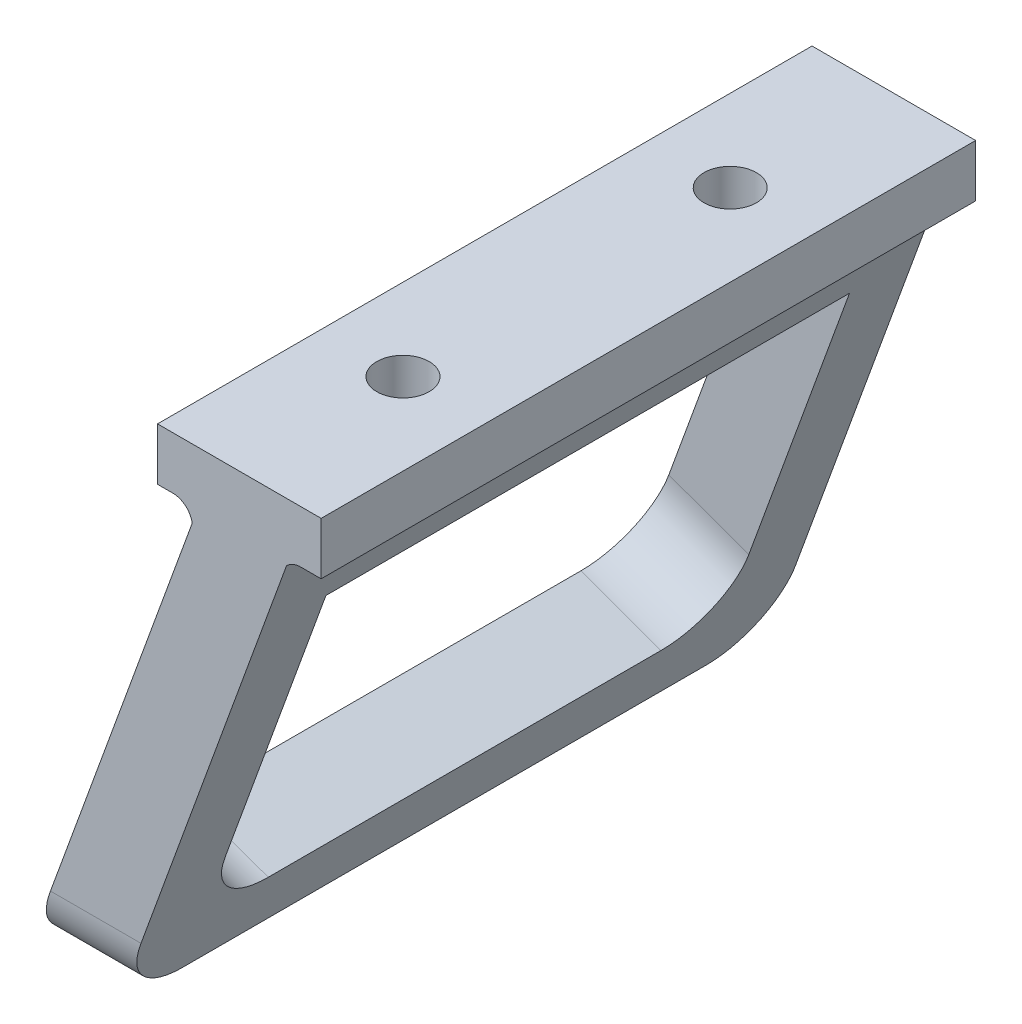
SolidWorks part; units mm, degrees
ref_plane "Front Plane" through (0, 0, 0) normal (0, 0, 1) x (1, 0, 0)
ref_plane "Top Plane" through (0, 0, 0) normal (0, 1, 0) x (1, 0, 0)
ref_plane "Right Plane" through (0, 0, 0) normal (1, 0, 0) x (0, 0, -1)
sketch "Sketch1" plane through (0, 0, 0) normal (0, 0, 1) x (1, 0, 0)
  line L0 (-12.5, 8) -> (12.5, 8)
  line L1 (12.5, 8) -> (12.5, 0)
  line L2 (12.5, 0) -> (9.3758, 0)
  line L3 (7.2, -0.9346) -> (-18.6657, -72)
  line L4 (-18.6657, -72) -> (-32.5, -72)
  line L5 (-32.5, -72) -> (-7.2, -2.4888)
  line L6 (-10.1561, 0) -> (-12.5, 0)
  line L7 (-12.5, 0) -> (-12.5, 8)
  arc A0 (-7.2, -2.4888) -> (-10.1561, 0) centre (-10.1561, -3) ccw
  arc A1 (9.3758, 0) -> (7.2, -0.9346) centre (9.3758, -3) ccw
  point P12 (0, 0)
  point P13 (0, 0)
  point P14 (12.5, 4)
  point P16 (-7.2, -2.9968)
  point P17 (-7.2, -2.9968)
  point P18 (0, 0)
  point P19 (0, 0)
  point P20 (7.2, -0.9346)
  point P21 (0, 0)
  dimension "D5" = 3
  dimension "D6" = 3
  dimension "D1" = 8
  dimension "D2" = 5.3
  dimension "D3" = 20
  dimension "D4" = 13
  dimension "D7" = 80
  dimension "D8" = 19.7
  dimension "D9" = 25
  dimension "D10" = 45
  dimension "D11" = 12.5
extrude "Boss-Extrude1" add sketch "Sketch1" along normal blind 50 and the other way blind 50
fillet "Fillet1" radius 10 2 edges at (-25.5828, -72, -50) (-25.5828, -72, 50)
sketch "Sketch2" plane through (-5.5579, 2.0229, 0) normal (-0.9397, 0.342, 0) x (0, 0, 1)
  line L1 (-40, -10.0299) -> (40, -10.0299)
  line L2 (-40, -10.0299) -> (-40, -55.0299)
  line L3 (-30, -65.0299) -> (30, -65.0299)
  line L4 (40, -10.0299) -> (40, -55.0299)
  line L7 (-40, -78.7735) -> (40, -78.7735) construction
  arc A0 (30, -65.0299) -> (40, -55.0299) centre (30, -55.0299) ccw
  arc A1 (-40, -55.0299) -> (-30, -65.0299) centre (-30, -55.0299) ccw
  dimension "D1" = 10
  dimension "D2" = 80
  dimension "D3" = 40
  dimension "D4" = 13.7437
  dimension "D5" = 55
extrude "Cut-Extrude2" cut sketch "Sketch2" against normal blind 50 contours L1 L4 A0 L3 A1 L2
sketch "Sketch3" plane through (0, 8, 0) normal (0, 1, 0) x (1, 0, 0)
  line L0 (12.5, 50) -> (12.5, -50) construction
  line L1 (12.5, -50) -> (-12.5, -50) construction
  point P0 (0, 25)
  point P2 (0, -25)
  point P9 (0, 0)
  dimension "D1" = 12.5
  dimension "D2" = 25
  dimension "D3" = 50
hole_wizard "Ø1.0mm Dowel Hole1" positions "Sketch3" profile "Sketch4" hole size "Ø1.0" standard "ISO"
sketch "Sketch4" plane through (0, 8, -25) normal (1, 0, 0) x (0, 0, 1)
  line L0 (0, 0) -> (0, 17.4034)
  line L1 (0, 17.4034) -> (4, 15)
  line L2 (4, 15) -> (4, 0)
  line L5 (4, 0) -> (0, 0)
  line L10 (0, 17.4034) -> (-4, 15) construction
  line L11 (0, -6.35) -> (0, 107.95) construction
  dimension "Hole Dia." = 8
  dimension "Hole Depth" = 15
  dimension "Drill Angle" = 118
